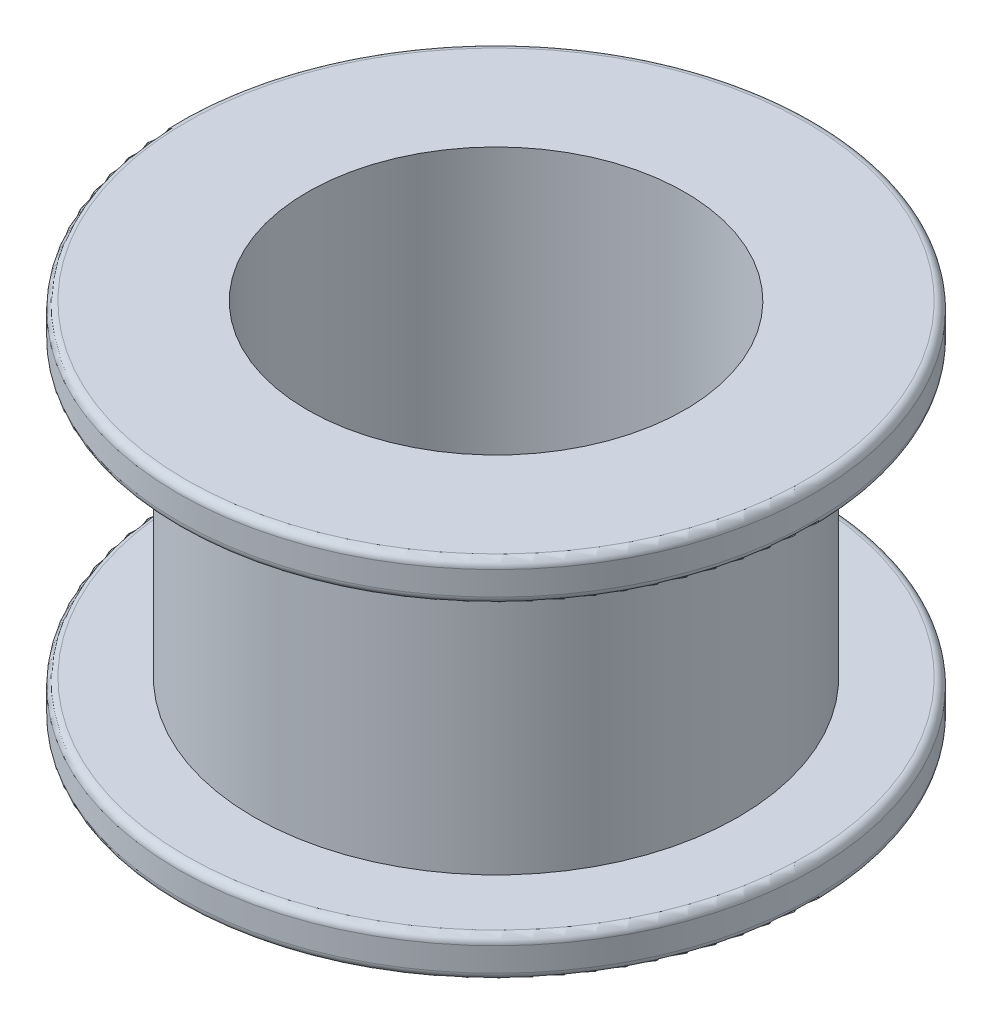
SolidWorks part; units mm, degrees
material "1060-H12 Válcovaný drát (SS)"
ref_plane "Front Plane" through (0, 0, 0) normal (0, 0, 1) x (1, 0, 0)
ref_plane "Top Plane" through (0, 0, 0) normal (0, 1, 0) x (1, 0, 0)
ref_plane "Right Plane" through (0, 0, 0) normal (1, 0, 0) x (0, 0, -1)
sketch "Esboço4" plane through (0, 0, 0) normal (0, 1, 0) x (1, 0, 0)
  circle A0 centre (0, 0) radius 4.75
  circle A1 centre (0, 0) radius 6.1
  circle A2 centre (0, 0) radius 8
  dimension "D1" = 9.5
  dimension "D2" = 12.2
  dimension "D3" = 16
extrude "Ressalto-extrusão3" add sketch "Esboço4" along normal blind 9.2 contours A1 A0 region at (-5.9275, 0, 0)
extrude "Ressalto-extrusão4" add sketch "Esboço4<3>" along normal blind 1 contours A2 A1 region at (-7.7737, 0, 0)
sketch "Esboço4<3>" plane through (0, 0, 0) normal (0, 1, 0) x (1, 0, 0) same geometry as "Esboço4"
sketch "Esboço5" plane through (0, 9.2, 0) normal (0, 1, 0) x (1, 0, 0)
  circle A0 centre (0, 0) radius 8
  circle A1 centre (0, 0) radius 4.75
extrude "Ressalto-extrusão6" add sketch "Esboço5" against normal blind 1
fillet "Filete5" radius 0.2 2 edges at (0, 9.2, 8) (0, 8.2, 8)
fillet "Filete6" radius 0.2 2 edges at (0, 0, 8) (0, 1, 8)
